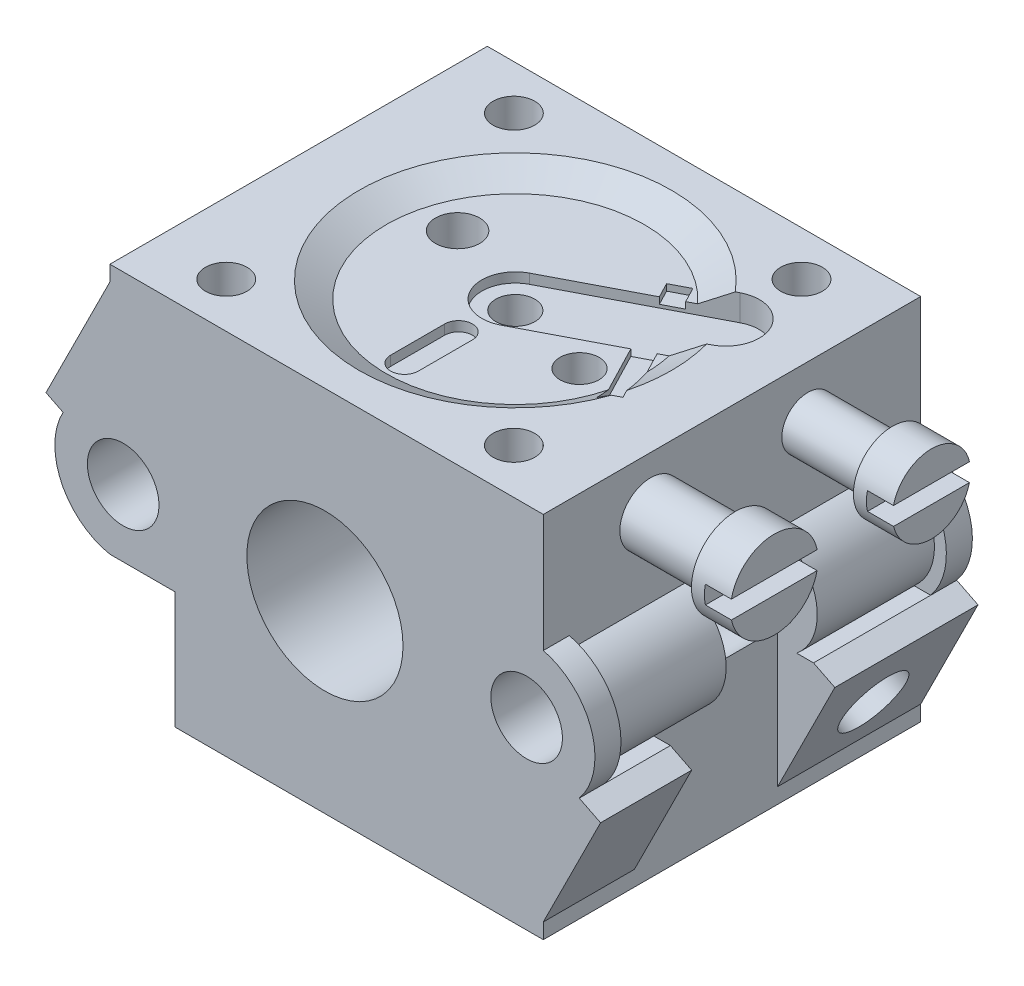
SolidWorks part; units mm, degrees
ref_plane "Front Plane" through (0, 0, 0) normal (0, 0, 1) x (1, 0, 0)
ref_plane "Top Plane" through (0, 0, 0) normal (0, 1, 0) x (1, 0, 0)
ref_plane "Right Plane" through (0, 0, 0) normal (1, 0, 0) x (0, 0, -1)
sketch "Sketch1" plane through (0, 0, 0) normal (0, 0, 1) x (1, 0, 0)
  line L0 (-16.5216, 14.1483) -> (16.7784, 14.1483)
  line L1 (16.7784, 14.1483) -> (16.7784, 5.0898)
  line L2 (-16.5216, -14.1517) -> (16.7784, -14.1517)
  line L3 (16.7784, -14.1517) -> (16.7784, -12.9706)
  line L4 (16.7784, -12.9706) -> (21.1796, -4.1683)
  line L5 (21.1796, -4.1683) -> (19.5423, -3.3496)
  line L6 (-16.5216, -14.1517) -> (-16.5216, -5.1517)
  line L7 (-16.5216, 14.1483) -> (-16.5216, 12.9671)
  line L8 (-16.5216, 12.9671) -> (-21.4312, 3.1478)
  line L9 (-21.4312, 3.1478) -> (-20.1213, 2.4928)
  line L10 (-0.0018, -0.0017) -> (-15.5018, -0.0017) construction
  line L11 (-0.0018, -0.0017) -> (-0.0018, 4.1303) construction
  line L12 (-0.0018, -8.5017) -> (-0.0018, -14.1517) construction
  line L13 (-6.7084, 14.1483) -> (-6.7084, -14.1517) construction
  circle A0 centre (0, 0) radius 6
  circle A1 centre (-15.5018, -0.0017) radius 2.75
  circle A2 centre (15.4982, -0.0017) radius 2.75
  arc A4 (-20.1213, 2.4928) -> (-16.5216, -5.1517) centre (-15.5018, -0.0017) ccw
  arc A5 (19.5423, -3.3496) -> (16.7784, 5.0898) centre (15.4982, -0.0017) ccw
  point P24 (-6.7084, -0.0017)
  point P27 (21.9657, -3.6632)
  point P28 (17.4623, -14.1517)
  point P29 (17.2018, -11.7397)
  point P30 (21.668, -4.4448)
  point P31 (21.4075, -4.3331)
  point P32 (-17.4488, 14.1483)
  point P33 (-21.4312, 3.1478)
  dimension "D2" = 12
  dimension "D4" = 5.5
  dimension "D5" = 2.5
  dimension "D6" = 2.5
  dimension "D8" = 33.3
  dimension "D3" = 28.3
  dimension "D7" = 9
extrude "Boss-Extrude1" add sketch "Sketch1" along normal blind 29
sketch "Sketch2" plane through (0, -14.1517, 0) normal (0, -1, 0) x (1, 0, 0)
  line L0 (-16.5216, 0) -> (16.7784, 0) construction
  line L1 (-16.5216, 29) -> (-16.5216, 0) construction
  line L2 (-16.5216, 29) -> (16.7784, 29) construction
  line L3 (16.7784, 29) -> (16.7784, 0) construction
  circle A0 centre (-14.0216, 2.5) radius 1.15
  circle A1 centre (14.2784, 26.5) radius 1.15
  dimension "D1" = 2.5
  dimension "D3" = 2.5
  dimension "D5" = 2.3
  dimension "D6" = 2.3
  dimension "D2" = 2.5
  dimension "D4" = 2.5
extrude "Cut-Extrude1" cut sketch "Sketch2" against normal blind 3.3
sketch "Sketch3" plane through (0, -14.1517, 0) normal (0, -1, 0) x (1, 0, 0)
  line L0 (14.7784, 19.9154) -> (14.7784, 3.0392)
  line L1 (13.7784, 2.0392) -> (8.8036, 2.0392)
  line L2 (7.8036, 3.0392) -> (7.8036, 3.5344)
  line L3 (7.2178, 4.9486) -> (4.8538, 7.3126)
  line L4 (4.2681, 8.7268) -> (4.2681, 16.8984)
  line L5 (5.2681, 17.8984) -> (9.0486, 17.8984)
  line L6 (10.3227, 18.3567) -> (13.1414, 20.6862)
  line L7 (16.7784, 29) -> (16.7784, 0) construction
  arc A0 (4.2681, 16.8984) -> (5.2681, 17.8984) centre (5.2681, 16.8984) cw
  arc A1 (8.8036, 2.0392) -> (7.8036, 3.0392) centre (8.8036, 3.0392) cw
  arc A2 (14.7784, 3.0392) -> (13.7784, 2.0392) centre (13.7784, 3.0392) cw
  arc A3 (14.7784, 19.9154) -> (13.1414, 20.6862) centre (13.7784, 19.9154) ccw
  arc A4 (9.0486, 17.8984) -> (10.3227, 18.3567) centre (9.0486, 19.8984) ccw
  arc A5 (4.8538, 7.3126) -> (4.2681, 8.7268) centre (6.2681, 8.7268) cw
  arc A6 (7.8036, 3.5344) -> (7.2178, 4.9486) centre (5.8036, 3.5344) ccw
  point P11 (4.2681, 17.8984)
  point P16 (14.7784, 2.0392)
  point P19 (14.7784, 22.0392)
  point P22 (9.7681, 17.8984)
  point P25 (4.2681, 7.8984)
  point P28 (7.8036, 4.3628)
  dimension "D7" = 1
  dimension "D8" = 2
  dimension "D1" = 20
  dimension "D2" = 2
  dimension "D3" = 6.5
  dimension "D4" = 5.5
  dimension "D5" = 10
  dimension "D6" = 5
extrude "Cut-Extrude2" cut sketch "Sketch3" against normal blind 1.2
sketch "Sketch4" plane through (0, -12.9517, 0) normal (0, -1, 0) x (1, 0, 0)
  line L0 (4.2681, 11.7241) -> (5.7681, 11.7241) construction
  line L1 (4.2681, 16.8984) -> (4.2681, 8.7268) construction
  circle A0 centre (9.5181, 11.7241) radius 3.75
  point P6 (9.5815, 11.7241)
  dimension "D1" = 7.5
extrude "Cut-Extrude3" cut sketch "Sketch4" against normal blind 5.5
fillet "Fillet1" radius 0.4 15 edges at (9.7256, -12.9517, 18.0164) (11.732, -12.9517, 19.5215) (14.2044, -12.9517, 20.8201) (14.7784, -12.9517, 11.4773) (14.4855, -12.9517, 2.3321) (11.291, -12.9517, 2.0392) (8.0965, -12.9517, 2.3321) (7.8036, -12.9517, 3.2868) (7.6514, -12.9517, 4.2998) (6.0358, -12.9517, 6.1306) (4.4203, -12.9517, 7.9614) (4.2681, -12.9517, 12.8126) (4.561, -12.9517, 17.6055) (9.5181, -12.9517, 7.9741) (7.1583, -12.9517, 17.8984)
sketch "Sketch5" plane through (0, -14.1517, 0) normal (0, -1, 0) x (1, 0, 0)
  line L0 (-16.5216, 29) -> (-16.5216, 0) construction
  line L1 (-16.5216, 29) -> (-16.5216, 0) construction
  line L2 (-11.5216, 27.6514) -> (-11.5216, 29.7011)
  line L3 (-11.5216, 29.7011) -> (-18.1114, 29.7011)
  line L4 (-18.1114, 29.7011) -> (-18.1114, 11.7988)
  line L5 (-18.1114, 11.7988) -> (-16.5216, 11.7988)
  spline S0 degree 3 poles (-16.5216, 11.7988) (-16.5216, 15.2959) (-16.995, 21.518) (-13.386, 26.4524) (-11.5216, 27.6514) knots 0 0 0 0 0.621929 1 1 1 1
  dimension "D1" = 5
extrude "Cut-Extrude4" cut sketch "Sketch5" against normal up to vertex (9 mm away) up to point (-16.5216, -5.1517, 29)
sketch "Sketch6" plane through (0, -14.1517, 0) normal (0, -1, 0) x (1, 0, 0)
  line L3 (-14.0216, 16.8542) -> (-14.0216, 0)
  line L4 (-14.0216, 16.8542) -> (-14.0216, 6.15)
  line L5 (-4.6774, 2.5) -> (-4.6774, 6.15)
  line L6 (-16.5216, 2.5) -> (16.7784, 2.5)
  line L7 (-10.3716, 2.5) -> (-4.6774, 2.5)
  line L8 (-4.6774, 6.15) -> (-2.3104, 9.313)
  line L9 (-1.478, 17.6912) -> (-1.478, 24.4414)
  line L10 (-10.1693, 25.5486) -> (-8.69, 26.5)
  line L11 (-8.69, 26.5) -> (-4.0102, 26.5)
  line L12 (-11.5216, 29) -> (16.7784, 29) construction
  arc A1 (-1.478, 17.6912) -> (-2.3104, 9.313) centre (-0.312, 13.3449) ccw
  circle A2 centre (-14.0216, 2.5) radius 3.65
  arc A3 (-10.3716, 2.5) -> (-14.0216, 6.15) centre (-14.0216, 2.5) ccw
  arc A4 (-4.0102, 26.5) -> (-1.478, 24.4414) centre (-1.478, 27.028) ccw
  spline S5 degree 3 poles (-855.3284, -2844.1249) (189.1992, -110.999) (10.5569, 51.8456) (-12.3332, 23.4176) (-12.7457, 22.7203) (-13.2189, 21.6091) (-13.3521, 21.2287) (-13.5797, 20.4319) (-13.6735, 20.0175) (-20.9923, -21.1961) (131.6818, -196.7104) (-2455.4259, 1757.4527) knots -11.208202 -11.208202 -11.208202 -11.208202 0.25 0.25 0.5 0.5 0.625 0.625 0.75 0.75 12.624627 12.624627 12.624627 12.624627 only from (-10.1693, 25.5486) to (-14.0216, 16.8542)
  spline S6 degree 3 poles (-10.1693, 25.5486) (-10.7925, 25.1479) (-11.3557, 24.6316) (-12.3332, 23.4176) (-12.7457, 22.7203) (-13.2189, 21.6091) (-13.3521, 21.2287) (-13.5797, 20.4319) (-13.6735, 20.0175) (-13.9022, 18.7295) (-13.9838, 17.8111) (-14.0216, 16.8542) knots 0 0 0 0 0.25 0.25 0.5 0.5 0.625 0.625 0.75 0.75 1 1 1 1
  point P20 (-1.5305, 24.2877)
  point P21 (-4.6774, 6.15)
  dimension "D4" = 4.5
  dimension "D5" = 2.5
  dimension "D1" = 2.5
  dimension "D2" = 2.5
  dimension "D3" = 2.5
extrude "Cut-Extrude5" cut sketch "Sketch6" against normal blind 2
fillet "Fillet2" radius 2 10 edges at (-11.4406, -12.1517, 5.0809) (-7.5245, -12.1517, 2.5) (-4.6774, -12.1517, 4.325) (-3.4939, -12.1517, 7.7315) (-4.7899, -12.1517, 13.7898) (-1.478, -12.1517, 21.0663) (-3.1097, -12.1517, 25.021) (-6.3501, -12.1517, 26.5) first distance on face at (-11.8186, -13.1517, 4.703) first distance on face at (-7.5245, -13.1517, 2.5) first distance on face at (-4.6774, -13.1517, 4.325) first distance on face at (-3.4939, -13.1517, 7.7315) first distance on face at (-3.3421, -13.1517, 13.6459) first distance on face at (-1.478, -13.1517, 21.0663) first distance on face at (-2.9269, -13.1517, 25.2458) first distance on face at (-6.3501, -13.1517, 26.5) first distance on face at (-11.1324, -12.6517, 23.375) first distance on face at (-9.0598, -12.9017, 26.2622)
sketch "Sketch7" plane through (0, -12.1517, 0) normal (0, -1, 0) x (1, 0, 0)
  line L0 (-1.478, 17.6911) -> (-1.478, 24.4414) construction
  line L4 (-1.478, 22.2691) -> (-1.478, 20.0681)
  line L5 (-4.6774, 2.5) -> (-4.6774, 6.15) construction
  line L7 (-8.067, 4.8823) -> (-8.067, 4.1775)
  line L9 (-4.6774, 5.5811) -> (-4.6774, 3.4787)
  line L10 (-4.6774, 5.5811) -> (-8.067, 4.8823)
  line L11 (-4.6774, 3.4787) -> (-8.067, 4.1775)
  line L12 (-8.067, 4.5299) -> (-4.6774, 4.5299) construction
  line L13 (-1.478, 22.2691) -> (-4.3852, 21.4568)
  line L14 (-4.3852, 21.4568) -> (-4.3852, 20.8805)
  line L15 (-4.3852, 20.8805) -> (-1.478, 20.0681)
  line L16 (-4.3852, 21.1686) -> (-1.478, 21.1686) construction
extrude "Cut-Extrude6" cut sketch "Sketch7" along normal blind 2
sketch "Sketch8" plane through (-1.478, 0, 0) normal (-1, 0, 0) x (0, 0, 1)
  line L0 (20.0681, -14.1517) -> (22.2691, -12.1517) construction
  line L1 (5.7018, -13.6786) -> (3.4204, -12.6249) construction
  circle A0 centre (4.5611, -13.1517) radius 0.6
  circle A1 centre (21.1686, -13.1517) radius 0.6
  point P10 (4.5611, -13.1517)
  dimension "D1" = 1.2
  dimension "D2" = 1.2
extrude "Cut-Extrude7" cut sketch "Sketch8" against normal blind 2 and the other way blind 6
sketch "Sketch9" plane through (0, -14.1517, 0) normal (0, -1, 0) x (1, 0, 0)
  line L0 (-1.478, 17.6911) -> (-4.7523, 14.075) construction
  line L1 (-2.3104, 9.313) -> (-4.7523, 14.075) construction
  line L2 (-3.5314, 11.694) -> (-0.3121, 13.3449) construction
  line L3 (-3.1152, 15.883) -> (-0.3121, 13.3449) construction
  circle A0 centre (-0.3121, 13.3449) radius 1.75
  spline S0 degree 3 poles (-2.3104, 9.313) (-2.5949, 9.4541) (-2.8644, 9.6252) (-3.5035, 10.1334) (-3.8419, 10.5095) (-4.3773, 11.3517) (-4.5742, 11.8176) (-4.8053, 12.7885) (-4.8393, 13.2932) (-4.7406, 14.2863) (-4.608, 14.7745) (-4.1904, 15.6809) (-3.9056, 16.099) (-3.215, 16.8193) (-2.8092, 17.1215) (-2.0827, 17.4941) (-1.7847, 17.6088) (-1.478, 17.6911) knots 0.46016 0.46016 0.46016 0.46016 0.671853 0.671853 1.004508 1.004508 1.337163 1.337163 1.669818 1.669818 2.002473 2.002473 2.335128 2.335128 2.667783 2.667783 2.879476 2.879476 2.879476 2.879476 weights 1 1 1 1 1 1 1 1 1 1 1 1 1 1 1 1 1 1 construction
extrude "Cut-Extrude8" cut sketch "Sketch9" against normal blind 8
sketch "Sketch10" plane through (0, -14.1517, 0) normal (0, -1, 0) x (1, 0, 0)
  circle A0 centre (1.1718, 4.497) radius 1.15
  circle A1 centre (1.1718, 8.1434) radius 1.15
  circle A2 centre (1.1718, 21.1411) radius 1.15
  circle A3 centre (-1.6862, 26.7368) radius 1.15
  circle A4 centre (6.1122, 22.6384) radius 1.15
  point P10 (7.1505, 22.9918)
  point P11 (-1.6862, 26.7368)
  point P12 (1.1718, 4.497)
  point P13 (2.5312, 21.2014)
  point P14 (1.1718, 21.1411)
  point P15 (6.1122, 22.6384)
  dimension "D1" = 2.3
  dimension "D2" = 2.3
  dimension "D3" = 2.3
  dimension "D4" = 2.3
  dimension "D5" = 2.3
extrude "Cut-Extrude9" cut sketch "Sketch10" against normal blind 6
sketch "Sketch12" plane through (16.7784, 0, 0) normal (1, 0, 0) x (0, 0, -1)
  line L0 (-29, -3.3496) -> (-22, -3.3496) construction
  line L1 (-29, -3.3496) -> (0, -3.3496) construction
  line L2 (0, -3.3496) -> (-11, -3.3496) construction
  line L3 (-29, 5.0898) -> (0, 5.0898) construction
  line L5 (-11, -3.3496) -> (-11, 5.0898)
  line L6 (-11, 5.0898) -> (-18, 5.0898)
  line L7 (-18, -3.3496) -> (-18, 5.0898)
  line L8 (-29, -12.9706) -> (0, -12.9706) construction
  line L9 (-22, -3.3496) -> (-18, -3.3496)
  line L10 (-22, -3.3496) -> (-22, -12.9706)
  line L11 (-22, -12.9706) -> (-11, -12.9706)
  line L12 (-11, -3.3496) -> (-11, -12.9706)
  dimension "D1" = 7
  dimension "D2" = 11
  dimension "D3" = 7
extrude "Cut-Extrude10" cut sketch "Sketch12" along normal blind 16
sketch "Sketch13" plane through (0, 0, 11) normal (0, 0, 1) x (1, 0, 0)
  line L0 (19.5423, -3.3496) -> (16.7784, -3.3496) construction
  line L2 (16.7784, 5.0898) -> (16.7784, 2.4321) construction
  line L3 (19.5423, -3.3496) -> (18.2466, -3.3496)
  line L5 (16.7784, 5.0898) -> (16.7784, 4.1362)
  arc A2 (18.2466, -3.3496) -> (16.7784, 4.1362) centre (15.4982, -0.0017) ccw
  arc A3 (19.5423, -3.3496) -> (16.7784, 5.0898) centre (15.4982, -0.0017) ccw construction
  arc A4 (19.5423, -3.3496) -> (16.7784, 5.0898) centre (15.4982, -0.0017) ccw
extrude "Cut-Extrude11" cut sketch "Sketch13" against normal blind 9 and the other way blind 16
sketch "Sketch14" plane through (16.7784, 0, 0) normal (1, 0, 0) x (0, 0, -1)
  circle A0 centre (-20.7529, 10.1028) radius 2.365
  circle A1 centre (-8.6724, 10.1028) radius 2
  point P4 (-20.1858, 10.1028)
  point P5 (-8.6724, 10.1028)
  point P6 (-20.7529, 10.1028)
  dimension "D1" = 4.73
  dimension "D2" = 4
extrude "Boss-Extrude2" add sketch "Sketch14" along normal blind 6.5
sketch "Sketch15" plane through (23.2784, 0, 0) normal (1, 0, 0) x (0, 0, -1)
  circle A0 centre (-20.7529, 10.1028) radius 3.365
  circle A1 centre (-8.6724, 10.1028) radius 3
  circle A2 centre (-8.6724, 10.1028) radius 2 construction
  circle A3 centre (-20.7529, 10.1028) radius 2.365 construction
  dimension "D1" = 1
  dimension "D2" = 1
extrude "Boss-Extrude3" add sketch "Sketch15" along normal blind 3
sketch "Sketch16" plane through (26.2784, 0, 0) normal (1, 0, 0) x (0, 0, -1)
  line L1 (-25.0917, 10.7833) -> (-16.5843, 10.7833)
  line L2 (-25.0917, 10.7833) -> (-25.0917, 9.3938)
  line L3 (-25.0917, 9.3938) -> (-16.5843, 9.3938)
  line L4 (-16.5843, 10.7833) -> (-16.5843, 9.3938)
  line L5 (-12.6142, 10.7833) -> (-3.9933, 10.7833)
  line L6 (-12.6142, 10.7833) -> (-12.6142, 9.3938)
  line L7 (-12.6142, 9.3938) -> (-3.9933, 9.3938)
  line L8 (-3.9933, 10.7833) -> (-3.9933, 9.3938)
  point P8 (-11.1112, 10.9535)
extrude "Cut-Extrude12" cut sketch "Sketch16" against normal blind 2
sketch "Sketch17" plane through (0, 0, 0) normal (0, 0, -1) x (-1, 0, 0)
  circle A0 centre (0, -10.1601) radius 1.25
  point P2 (0, -10.1601)
extrude "Cut-Extrude13" cut sketch "Sketch17" against normal blind 5
sketch "Sketch18" plane through (0, 14.1483, 0) normal (0, 1, 0) x (1, 0, 0)
  line L0 (-16.5216, -14.5) -> (16.7784, -14.5) construction
  line L1 (-16.5216, -29) -> (-16.5216, 0) construction
  line L2 (16.7784, -29) -> (16.7784, 0) construction
  circle A0 centre (0.1284, -14.5) radius 12
extrude "Cut-Extrude14" cut sketch "Sketch18" against normal blind 1.25
sketch "Sketch19" plane through (0, 14.1483, 0) normal (0, 1, 0) x (1, 0, 0)
  line L0 (11.05, -3.4316) -> (11.05, -25.5316) construction
  line L1 (0, -14.4816) -> (0, -12.4816) construction
  line L2 (11.05, -25.5316) -> (-11.05, -25.5316) construction
  line L3 (-12.65, -3.4316) -> (12.65, -3.4316) construction
  line L4 (-11.05, -1.8316) -> (-11.05, -27.1316) construction
  line L9 (0, -14.4816) -> (-11.05, -14.4816) construction
  line L10 (0, -14.4816) -> (0, -3.4316) construction
  line L11 (0, -3.4316) -> (0, -14.4816) construction
  line L12 (0, -14.4816) -> (11.05, -14.4816) construction
  line L13 (11.05, -14.4816) -> (0, -14.4816) construction
  line L14 (0, -14.4816) -> (0, -25.5316) construction
  line L15 (11.05, -25.5316) -> (-11.05, -3.4316) construction
  line L16 (11.05, -3.4316) -> (-11.05, -25.5316) construction
  line L17 (0, -3.4316) -> (0, -3.4651) construction
  circle A1 centre (-11.05, -3.4316) radius 1.6
  circle A2 centre (11.05, -3.4316) radius 1.6
  circle A3 centre (-11.05, -25.5316) radius 1.6
  circle A4 centre (11.05, -25.5316) radius 1.6
extrude "Cut-Extrude15" cut sketch "Sketch19" against normal blind 7.2
chamfer "Chamfer1" distance 1.25 angle 59 1 edges at (-11.8716, 12.8983, 14.5) first distance on face at (-11.8716, 12.8983, 14.5)
sketch "Sketch21" plane through (0, 12.8983, 0) normal (0, 1, 0) x (1, 0, 0)
  line L0 (0.1284, -14.5) -> (10.7782, -8.9698) construction
  line L1 (-1.0565, -12.2182) -> (9.5933, -6.688)
  line L2 (1.3133, -16.7818) -> (11.9631, -11.2517)
  line L3 (0.1284, -23.0149) -> (0.1284, -18.8586) construction
  line L4 (-0.9346, -23.0149) -> (-0.9346, -18.8586)
  line L5 (1.1914, -23.0149) -> (1.1914, -18.8586)
  circle A0 centre (-6.643, -12.1644) radius 1.7
  circle A1 centre (0.1284, -14.5) radius 12 construction
  arc A2 (-1.0565, -12.2182) -> (1.3133, -16.7818) centre (0.1284, -14.5) ccw
  arc A3 (11.9631, -11.2517) -> (9.5933, -6.688) centre (10.7782, -8.9698) ccw
  arc A4 (-0.9346, -23.0149) -> (1.1914, -23.0149) centre (0.1284, -23.0149) ccw
  arc A5 (1.1914, -18.8586) -> (-0.9346, -18.8586) centre (0.1284, -18.8586) ccw
  point P7 (5.4533, -11.7349)
  point P12 (0.1284, -20.9367)
extrude "Cut-Extrude16" cut sketch "Sketch21" against normal blind 0.75 and the other way blind 7.2
sketch "Sketch22" plane through (0, 12.1483, 0) normal (0, 1, 0) x (1, 0, 0)
  circle A0 centre (-6.643, -12.1644) radius 1.7
  circle A1 centre (0.1284, -14.5) radius 1.5
extrude "Cut-Extrude17" cut sketch "Sketch22" against normal blind 3
sketch "Sketch23" plane through (0, 12.8983, 0) normal (0, 1, 0) x (1, 0, 0)
  line L0 (4.9096, -7.6578) -> (10.715, -18.8375)
  line L1 (1.3133, -16.7818) -> (11.9631, -11.2517) construction
  line L2 (4.9096, -7.6578) -> (6.2409, -6.9666)
  line L3 (6.2409, -6.9666) -> (12.0462, -18.1462)
  line L4 (12.0462, -18.1462) -> (10.715, -18.8375)
  dimension "D1" = 1.5
extrude "Cut-Extrude18" cut sketch "Sketch23" along normal blind 3 and the other way blind 0.5
sketch "Sketch24" plane through (0, 12.8983, 0) normal (0, 1, 0) x (1, 0, 0)
  circle A0 centre (7.2154, -16.6541) radius 1.5
  dimension "D1" = 3
extrude "Cut-Extrude19" cut sketch "Sketch24" against normal blind 4
sketch "Sketch25" plane through (-18.4041, 9.202, 0) normal (-0.8944, 0.4472, 0) x (0, 0, 1)
  circle A0 centre (5.6129, 0.3039) radius 2.5
  point P0 (5.6129, 0.3039)
  point P5 (5.5, -1.2797)
extrude "Cut-Extrude20" cut sketch "Sketch25" against normal blind 54
